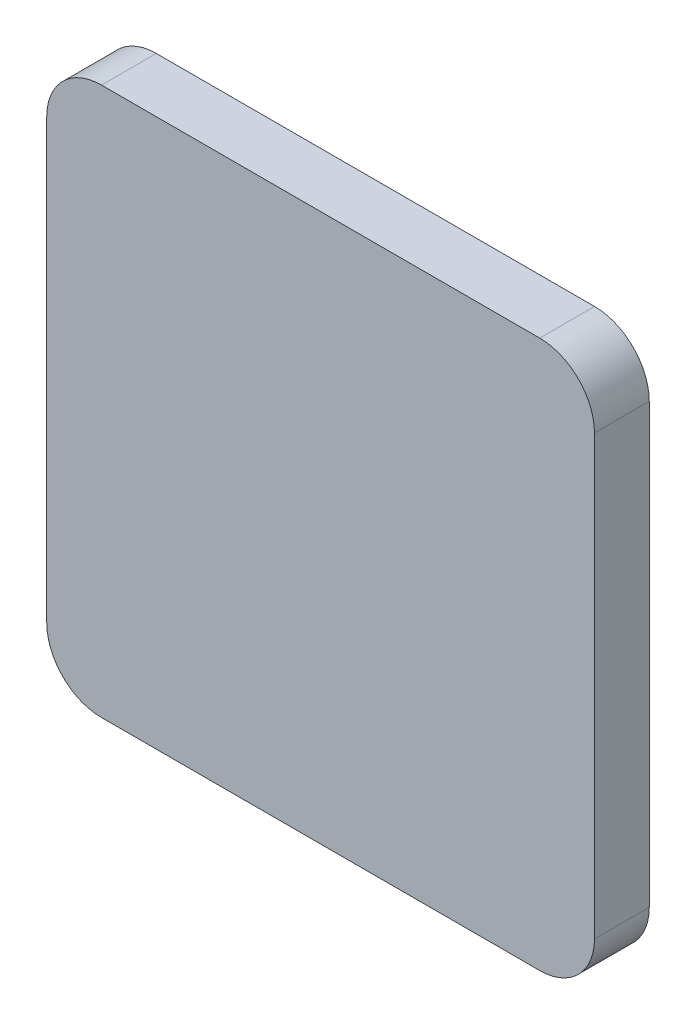
SolidWorks part; units mm, degrees
ref_plane "Front Plane" through (0, 0, 0) normal (0, 0, 1) x (1, 0, 0)
ref_plane "Top Plane" through (0, 0, 0) normal (0, 1, 0) x (1, 0, 0)
ref_plane "Right Plane" through (0, 0, 0) normal (1, 0, 0) x (0, 0, -1)
sketch "Sketch1" plane through (0, 0, 0) normal (0, 0, 1) x (1, 0, 0)
  line L0 (90, -80) -> (90, 80) construction
  line L1 (-80, -90) -> (80, -90) construction
  line L2 (-90, -80) -> (-90, 80) construction
  line L3 (-80, 90) -> (80, 90) construction
  line L4 (-80, 90) -> (80, 90)
  line L5 (-90, -80) -> (-90, 80)
  line L6 (-80, -90) -> (80, -90)
  line L7 (90, -80) -> (90, 80)
  line L8 (-80, -100) -> (80, -100)
  line L9 (100, -80) -> (100, 80)
  line L10 (-80, 100) -> (80, 100)
  line L11 (-100, -80) -> (-100, 80)
  arc A0 (80, -90) -> (90, -80) centre (80, -80) ccw construction
  arc A1 (-90, -80) -> (-80, -90) centre (-80, -80) ccw construction
  arc A2 (-80, 90) -> (-90, 80) centre (-80, 80) ccw construction
  arc A3 (90, 80) -> (80, 90) centre (80, 80) ccw construction
  arc A4 (90, 80) -> (80, 90) centre (80, 80) ccw
  arc A5 (-80, 90) -> (-90, 80) centre (-80, 80) ccw
  arc A6 (-90, -80) -> (-80, -90) centre (-80, -80) ccw
  arc A7 (80, -90) -> (90, -80) centre (80, -80) ccw
  arc A8 (80, -100) -> (100, -80) centre (80, -80) ccw
  arc A9 (100, 80) -> (80, 100) centre (80, 80) ccw
  arc A10 (-80, 100) -> (-100, 80) centre (-80, 80) ccw
  arc A11 (-100, -80) -> (-80, -100) centre (-80, -80) ccw
  dimension "D1" = 10
extrude "Boss-Extrude1" add sketch "Sketch1" along normal blind 10 contours L6 A7 L7 A4 L4 A5 L5 A6 | L11 A11 L8 A8 L9 A9 L10 A10 A7 L6 A6 L5 A5 L4 A4 L7 region at (0, 0, 0) region at (-92.1421, -92.1421, 0)
extrude "Boss-Extrude2" add sketch "Sketch1<3>" against normal blind 10
sketch "Sketch1<3>" plane through (0, 0, 0) normal (0, 0, 1) x (1, 0, 0) same geometry as "Sketch1"
sketch "Sketch3" plane through (0, 0, 0) normal (0, 1, 0) x (1, 0, 0)
  line L0 (80, 0) -> (-80, 0) construction
  line L1 (80, 0) -> (-80, 0)
  line L2 (0, 0) -> (-25.0807, 43.6947)
  line L3 (-25.0807, 43.6947) -> (-57.5896, 43.6947)
  line L4 (-57.5896, 43.6947) -> (-32.5088, 0)
  line L5 (-32.5088, 0) -> (32.5088, 0)
  line L6 (0, 0) -> (0, 43.6947) construction
  line L7 (57.5896, 43.6947) -> (32.5088, 0)
  line L8 (25.0807, 43.6947) -> (57.5896, 43.6947)
  line L9 (0, 0) -> (25.0807, 43.6947)
extrude "Boss-Extrude3" add sketch "Sketch3" along normal mid plane 60 contours L3 L4 L1 L2 | L9 L1 L7 L8 region at (-28.7948, 0, -21.8473) region at (28.7948, 0, -21.8473)
fillet "Fillet1" radius 10 6 edges at (-16.2544, -30, 0) (16.2544, 30, 0) (16.2544, -30, 0) (32.5088, 0, 0) (-32.5088, 0, 0) (-16.2544, 30, 0)
fillet "Fillet2" radius 7 1 edges at (0, 0, 0)
